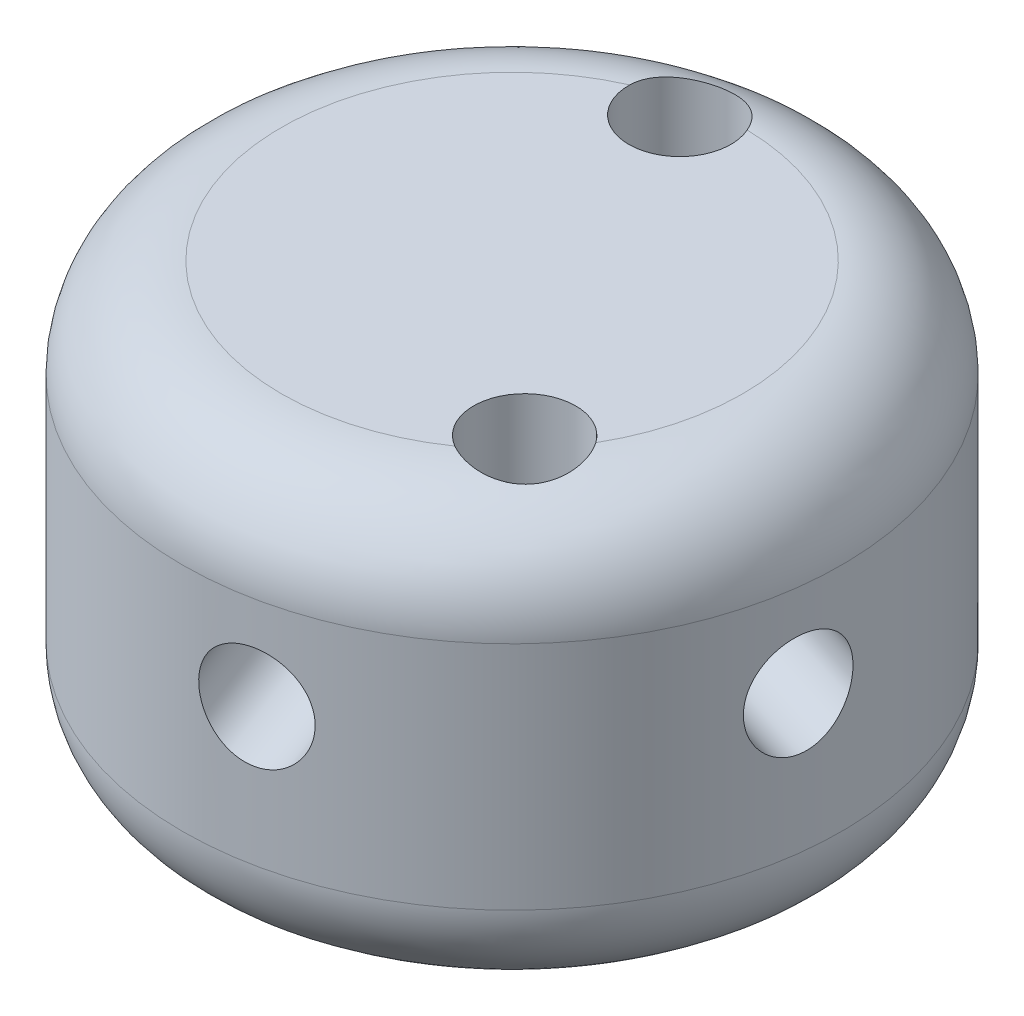
SolidWorks part; units mm, degrees
ref_plane "Front Plane" through (0, 0, 0) normal (0, 0, 1) x (1, 0, 0)
ref_plane "Top Plane" through (0, 0, 0) normal (0, 1, 0) x (1, 0, 0)
ref_plane "Right Plane" through (0, 0, 0) normal (1, 0, 0) x (0, 0, -1)
sketch "Sketch1" plane through (0, 0, 0) normal (0, 1, 0) x (1, 0, 0)
  circle A0 centre (0, 0) radius 10
  dimension "D1" = 20
extrude "Boss-Extrude1" add sketch "Sketch1" along normal blind 3 and the other way blind 10
ref_axis "5hubaxis" through (0, 5.5, 0) along (0, -1, 0)
ref_plane "holeplane" through (-3.3529, -1.0931, 1.8877) normal (0.8382, 0.2733, -0.4719) x (-0.4487, -0.1463, -0.8816)
sketch "Sketch4" plane through (-3.3529, -1.0931, 1.8877) normal (0.8382, 0.2733, -0.4719) x (-0.4487, -0.1463, -0.8816)
  circle A0 centre (0, 0) radius 1.5 construction
  circle A1 centre (0, 0) radius 1.5
extrude "hole" cut sketch "Sketch4" against normal through all
pattern_circular "holecir" count 5 over 360 about axis through (0, 5.5, 0) along (0, -1, 0) of "hole"
sketch "Sketch5" plane through (0, -10, 0) normal (0, -1, 0) x (1, 0, 0)
  line L0 (-10, 0) -> (10, 0) construction
  circle A0 centre (0, 0) radius 10 construction
  text T0 "5"
extrude "Boss-Extrude2" [suppressed] add sketch "Sketch5" along normal blind 1
ref_plane "Plane1" through (0, -5, 0) normal (0, -1, 0) x (-1, 0, 0)
sketch "Sketch6" plane through (0, -5, 0) normal (0, -1, 0) x (-1, 0, 0)
  circle A0 centre (0, 0) radius 3.5
  dimension "D1" = 7
extrude "bearinghole" cut sketch "Sketch6" along normal blind 2.6
sketch "Sketch7" plane through (0, -5, 0) normal (0, -1, 0) x (-1, 0, 0)
  circle A0 centre (0, 0) radius 2.05
  dimension "D1" = 4.1
extrude "shafthole" cut sketch "Sketch7" along normal through all
sketch "Sketch8" plane through (0, 3, 0) normal (0, 1, 0) x (1, 0, 0)
  line L0 (-1.9732, 9.8034) -> (0, 0) construction
  line L1 (0, 0) -> (7.3586, -6.7713) construction
  line L2 (0, 0) -> (1.9732, -9.8034) construction
  line L3 (3.4214, -9.3965) -> (2.2297, -3.4761) construction
  line L4 (0, 0) -> (9.9333, -1.1528) construction
  line L5 (9.9939, 0.3502) -> (3.995, 1.0464) construction
  line L6 (0, 0) -> (4.166, 9.0909) construction
  line L7 (2.7552, 9.613) -> (0.2393, 4.1229) construction
  circle A0 centre (0, 0) radius 10 construction
  circle A1 centre (0, 0) radius 6.5 construction
  point P15 (-1.2826, 6.3722)
  point P16 (4.7831, -4.4014)
  dimension "D3" = 13
  dimension "D1" = 36
  dimension "D2" = 36
hole_wizard "Ø3.1 (3.1) Diameter Hole1" positions "Sketch9" profile "Sketch10" hole size "Ø3.1" standard "ISO" end condition through all
sketch "Sketch9" plane through (0, 3, 0) normal (0, 1, 0) x (1, 0, 0)
  point P0 (-1.2826, 6.3722)
  point P3 (4.7831, -4.4014)
sketch "Sketch10" plane through (-1.2826, 3, -6.3722) normal (1, 0, 0) x (0, 0, 1)
  line L0 (0, 0) -> (0, 13)
  line L1 (0, 13) -> (1.55, 13)
  line L2 (1.55, 13) -> (1.55, 0)
  line L5 (1.55, 0) -> (0, 0)
  line L11 (0, -6.35) -> (0, 107.95) construction
  dimension "Thru Hole Dia." = 3.1
  dimension "Thru Hole Depth" = 13
fillet "Fillet2" radius 3 2 edges at (0, 3, 10) (0, -10, 10)
ref_plane "Plane2" through (0, -6.25, 0) normal (0, -1, 0) x (-1, 0, 0)
